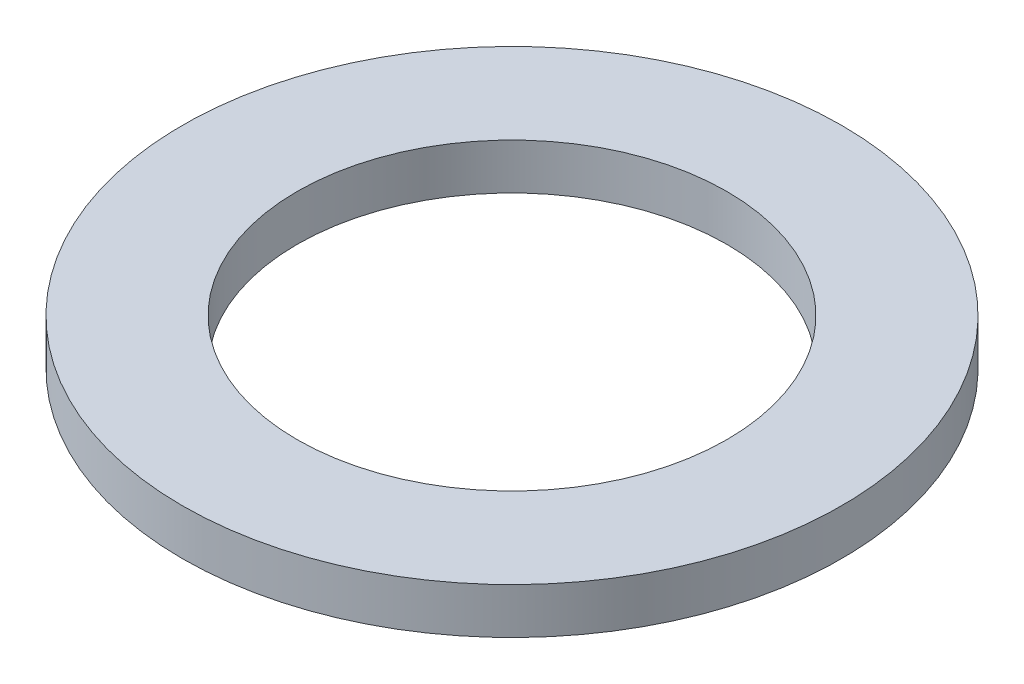
SolidWorks part; units mm, degrees
ref_plane "Front Plane" through (0, 0, 0) normal (0, 0, 1) x (1, 0, 0)
ref_plane "Top Plane" through (0, 0, 0) normal (0, 1, 0) x (1, 0, 0)
ref_plane "Right Plane" through (0, 0, 0) normal (1, 0, 0) x (0, 0, -1)
sketch "Sketch1" plane through (0, 0, 0) normal (0, 1, 0) x (1, 0, 0)
  circle A0 centre (0, 0) radius 57.5
  dimension "FLANGE_OD" = 115
extrude "Boss-Extrude1" add sketch "Sketch1" along normal blind 8
sketch "Sketch2" plane through (0, 0, 0) normal (0, 1, 0) x (1, 0, 0)
  circle A0 centre (0, 0) radius 37.5
  dimension "BORE_D" = 75
extrude "Cut-Extrude1" cut sketch "Sketch2" along normal through all
sketch "Sketch3" plane through (0, 8, 0) normal (0, 1, 0) x (1, 0, 0)
  circle A0 centre (0, 0) radius 22.6479 construction
  circle A1 centre (-22.6479, 0) radius 2.0321
  dimension "BOLT_D" = 4.0642
  dimension "BOLT_PCD" = 45.2958
extrude "Cut-Extrude2" cut sketch "Sketch3" against normal blind 5.4921 rebuild error yes
pattern_circular "CirPattern1" count 3 over 360 rebuild error yes
